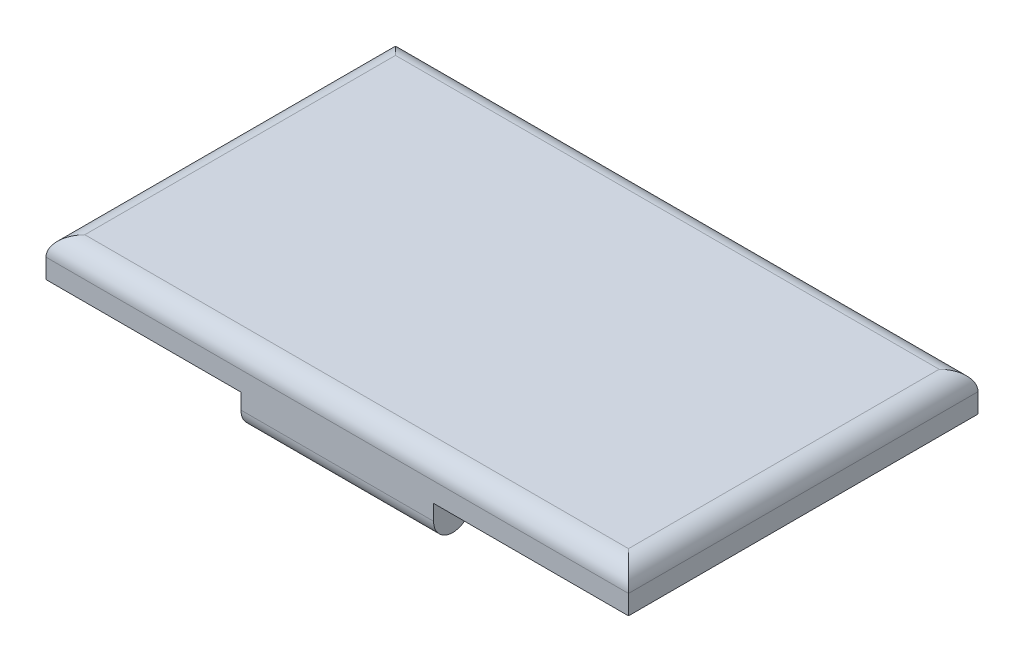
SolidWorks part; units mm, degrees
ref_plane "Front Plane" through (0, 0, 0) normal (0, 0, 1) x (1, 0, 0)
ref_plane "Top Plane" through (0, 0, 0) normal (0, 1, 0) x (1, 0, 0)
ref_plane "Right Plane" through (0, 0, 0) normal (1, 0, 0) x (0, 0, -1)
sketch "Sketch1" plane through (0, 0, 0) normal (0, 1, 0) x (1, 0, 0)
  line L1 (0, 0) -> (150, 0)
  line L2 (0, 0) -> (0, 90)
  line L3 (0, 90) -> (150, 90)
  line L4 (150, 0) -> (150, 90)
  dimension "D1" = 150
  dimension "D2" = 90
extrude "Boss-Extrude1" add sketch "Sketch1" along normal blind 10
sketch "Sketch4" plane through (0, 0, 0) normal (0, -1, 0) x (1, 0, 0)
  line L15 (0, -16) -> (150, -16)
  line L16 (6, -16) -> (144, -16)
  line L18 (150, -74) -> (0, -74)
  line L19 (144, -74) -> (6, -74)
  line L24 (6, -90) -> (6, 0)
  line L25 (6, -74) -> (6, -16)
  line L27 (144, 0) -> (144, -90)
  line L28 (144, -16) -> (144, -74)
  dimension "D1" = 16
  dimension "D2" = 16
  dimension "D3" = 6
  dimension "D4" = 6
sketch "Sketch2" plane through (0, 0, 0) normal (0, -1, 0) x (1, 0, 0)
  line L0 (0, 0) -> (150, 0) construction
  line L1 (50.2, 0) -> (99.8, 0)
  line L2 (50.2, 0) -> (50.2, -9.9)
  line L3 (50.2, -9.9) -> (99.8, -9.9)
  line L4 (99.8, 0) -> (99.8, -9.9)
  line L5 (0, -90) -> (0, 0) construction
  line L6 (150, 0) -> (150, -90) construction
  line L7 (0, -45) -> (150, -45) construction
  line L8 (99.8, -90) -> (99.8, -80.1)
  line L9 (50.2, -80.1) -> (99.8, -80.1)
  line L10 (50.2, -90) -> (50.2, -80.1)
  line L11 (50.2, -90) -> (99.8, -90)
  dimension "D1" = 50.2
  dimension "D2" = 50.2
  dimension "D3" = 9.9
extrude "Boss-Extrude2" add sketch "Sketch2" along normal blind 9
extrude "Cut-Extrude1" cut sketch "Sketch4" against normal blind 7
fillet "Fillet1" radius 5 8 edges at (75, -9, -80.1) (75, -9, -90) (75, -9, -9.9) (75, -9, 0) (150, 10, -45) (75, 10, -90) (75, 10, 0) (0, 10, -45)
